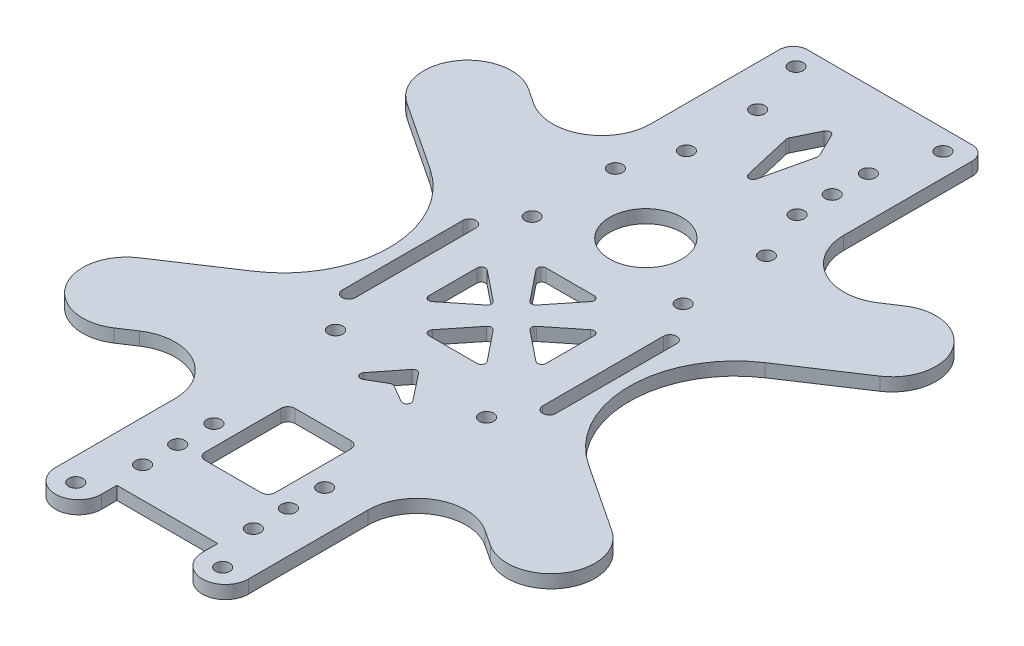
SolidWorks part; units mm, degrees
ref_plane "Front Plane" through (0, 0, 0) normal (0, 0, 1) x (1, 0, 0)
ref_plane "Top Plane" through (0, 0, 0) normal (0, 1, 0) x (1, 0, 0)
ref_plane "Right Plane" through (0, 0, 0) normal (1, 0, 0) x (0, 0, -1)
sketch "Sketch1" plane through (0, 0, 0) normal (0, 1, 0) x (1, 0, 0)
  line L0 (0, 68.8578) -> (0, -61.9125)
  line L1 (17.4625, -68.8578) -> (9.1281, -68.8578)
  line L2 (17.4625, -68.8578) -> (17.4625, -26.5137)
  line L3 (17.4625, 68.8578) -> (-17.4625, 68.8578)
  line L4 (-17.4625, -68.8578) -> (-17.4625, -26.5137)
  line L5 (17.4625, -68.8578) -> (-17.4625, 68.8578) construction
  line L6 (17.4625, 68.8578) -> (-17.4625, -68.8578) construction
  line L7 (9.1281, -68.8578) -> (9.1281, -61.9125)
  line L8 (9.1281, -61.9125) -> (-9.1281, -61.9125)
  line L9 (-9.1281, -68.8578) -> (-17.4625, -68.8578)
  line L10 (0, -16.2719) -> (6.8741, -25.0031)
  line L11 (-6.35, -50.0063) -> (6.35, -50.0063)
  line L12 (-6.35, -50.0063) -> (-6.35, -33.7344)
  line L13 (-6.35, -33.7344) -> (6.35, -33.7344)
  line L14 (6.35, -50.0063) -> (6.35, -33.7344)
  line L15 (-6.35, -50.0063) -> (6.35, -33.7344) construction
  line L16 (-6.35, -33.7344) -> (6.35, -50.0063) construction
  line L17 (6.8741, -25.0031) -> (0, -21.0344)
  line L18 (0, -2.7781) -> (5.9531, -10.2136)
  line L19 (5.9531, -10.2136) -> (-5.9531, -10.2136)
  line L20 (-5.9531, -10.2136) -> (0, -2.7781)
  line L21 (-10.6105, 6.35) -> (-3.175, 0.3969)
  line L22 (-3.175, 0.3969) -> (-10.6105, -5.5562)
  line L23 (-10.6105, -5.5562) -> (-10.6105, 6.35)
  line L24 (5.9531, 11.0073) -> (0, 3.5719)
  line L25 (0, 3.5719) -> (-5.9531, 11.0073)
  line L26 (-5.9531, 11.0073) -> (5.9531, 11.0073)
  line L27 (10.6105, -5.5563) -> (3.175, 0.3969)
  line L28 (3.175, 0.3969) -> (10.6105, 6.35)
  line L29 (10.6105, 6.35) -> (10.6105, -5.5563)
  line L30 (18.1511, 10.9234) -> (18.1511, -10.9234) construction
  line L31 (19.3417, 10.9234) -> (19.3417, -10.9234)
  line L32 (16.9605, 10.9234) -> (16.9605, -10.9234)
  line L33 (-55, 0) -> (55, 0) construction
  line L34 (0, 59.0292) -> (2.8661, 53.1453)
  line L35 (2.8661, 53.1453) -> (0, 40.773)
  line L36 (17.4625, 26.5137) -> (40.6519, 41.8703)
  line L37 (40.6519, 41.8703) -> (49.4171, 28.6344)
  line L38 (49.4171, 28.6344) -> (21.723, 10.2947)
  line L39 (49.4171, -28.6344) -> (21.723, -10.2947)
  line L40 (40.6519, -41.8703) -> (49.4171, -28.6344)
  line L41 (17.4625, -26.5137) -> (40.6519, -41.8703)
  line L42 (21.723, 10.2947) -> (21.723, -10.2947)
  line L43 (-17.4625, -26.5137) -> (-40.6519, -41.8703)
  line L44 (-40.6519, -41.8703) -> (-49.4171, -28.6344)
  line L45 (-49.4171, -28.6344) -> (-21.723, -10.2947)
  line L46 (-21.723, 10.2947) -> (-21.723, -10.2947)
  line L47 (-49.4171, 28.6344) -> (-21.723, 10.2947)
  line L48 (-40.6519, 41.8703) -> (-49.4171, 28.6344)
  line L49 (-17.4625, 26.5137) -> (-40.6519, 41.8703)
  line L50 (-9.1281, -68.8578) -> (-9.1281, -61.9125)
  line L51 (-18.1511, 10.9234) -> (-18.1511, -10.9234) construction
  line L52 (-19.3417, 10.9234) -> (-19.3417, -10.9234)
  line L53 (-16.9605, 10.9234) -> (-16.9605, -10.9234)
  line L54 (-2.8661, 53.1453) -> (0, 40.773)
  line L55 (0, 59.0292) -> (-2.8661, 53.1453)
  line L56 (17.4625, 26.5137) -> (17.4625, 68.8578)
  line L57 (-17.4625, 26.5137) -> (-17.4625, 68.8578)
  line L58 (-6.8741, -25.0031) -> (0, -21.0344)
  line L59 (0, -16.2719) -> (-6.8741, -25.0031)
  circle A0 centre (13.2953, -65.1867) radius 1.2898
  circle A1 centre (10.0211, -50.0063) radius 1.2898
  circle A2 centre (10.0211, -43.4578) radius 1.2898
  circle A3 centre (10.0211, -56.3563) radius 1.2898
  circle A4 centre (0, 24.6995) radius 6.5484
  circle A5 centre (10.0211, 54.9672) radius 1.2898
  circle A6 centre (10.0211, 48.4187) radius 1.2898
  circle A7 centre (10.0211, 42.0687) radius 1.2898
  arc A8 (19.3417, 10.9234) -> (16.9605, 10.9234) centre (18.1511, 10.9234) ccw
  arc A9 (16.9605, -10.9234) -> (19.3417, -10.9234) centre (18.1511, -10.9234) ccw
  circle A10 centre (13.671, -17.7895) radius 1.2898
  circle A11 centre (13.671, 17.7895) radius 1.2898
  circle A12 centre (13.671, 32.8707) radius 1.2898
  circle A13 centre (13.2953, 65.1867) radius 1.2898
  circle A14 centre (-13.2953, -65.1867) radius 1.2898
  circle A15 centre (-10.0211, -56.3562) radius 1.2898
  circle A16 centre (-10.0211, -50.0062) radius 1.2898
  circle A17 centre (-10.0211, -43.4578) radius 1.2898
  circle A18 centre (-13.671, -17.7895) radius 1.2898
  arc A19 (-19.3417, 10.9234) -> (-16.9605, 10.9234) centre (-18.1511, 10.9234) cw
  arc A20 (-16.9605, -10.9234) -> (-19.3417, -10.9234) centre (-18.1511, -10.9234) cw
  circle A21 centre (-13.671, 17.7895) radius 1.2898
  circle A22 centre (-13.671, 32.8707) radius 1.2898
  circle A23 centre (-10.0211, 42.0688) radius 1.2898
  circle A24 centre (-10.0211, 54.9672) radius 1.2898
  circle A25 centre (-13.2953, 65.1867) radius 1.2898
  point P0 (0, 0)
  point P10 (9.1281, -65.3852)
  point P17 (13.2953, -68.8578)
  point P18 (0, -41.8703)
  point P26 (18.1511, 0)
  point P46 (0, 0.3969)
  point P88 (0, -61.9125)
  point P100 (-18.1511, 0)
  point P111 (-10.0211, 48.4188)
  dimension "D4" = 2.5797
  dimension "D5" = 2.3813
  dimension "D11" = 10.3187
  dimension "D12" = 2.5797
  dimension "D13" = 2.5797
  dimension "D14" = 13.0969
  dimension "D23" = 7.1437
  dimension "D25" = 3.9688
  dimension "D27" = 1.1906
  dimension "D28" = 24.228
  dimension "D30" = 9.525
  dimension "D1" = 137.7156
  dimension "D2" = 34.925
  dimension "D3" = 8.3344
  dimension "D6" = 6.9453
  dimension "D7" = 16.2719
  dimension "D8" = 12.7
  dimension "D9" = 11.9062
  dimension "D10" = 2.3813
  dimension "D15" = 12.7
  dimension "D16" = 7.9375
  dimension "D17" = 11.1125
  dimension "D18" = 4.7625
  dimension "D19" = 9.525
  dimension "D20" = 11.9062
  dimension "D21" = 2.7781
  dimension "D26" = 6.35
  dimension "D29" = 6.35
  dimension "D31" = 2
  dimension "D32" = 9.525
  dimension "D33" = 18.2562
  dimension "D34" = 12.7
  dimension "D35" = 6.5448
  dimension "D36" = 15.875
  dimension "D37" = 26.9875
  dimension "D38" = 2.3813
  dimension "D24" = 2
  dimension "D22" = 4
extrude "Boss-Extrude1" add sketch "Sketch1" along normal mid plane 2.3813 contours A4 L0 L54 L55 L3 L57 L49 L48 L47 L46 L45 L44 L43 L4 L9 L50 L8 L11 L12 L13 L19 L20 L25 L26 A25 A23 A22 A21 A17 A15 L22 L23 L21 A14 A16 | A4 L0 L26 L24 L18 L19 L10 L17 L13 L14 L11 L8 L7 L1 L2 L41 L40 L39 L42 L38 L37 L36 L56 L3 L34 L35 A12 L28 L29 L27 A0 A1 A2 A3 A5 A6 region at (8.7312, 0, -67.3947) region at (-1.4631, 0, -63.9435)
fillet "Fillet1" 2 edges at (-17.4625, 0, 68.8578) (-9.1281, 0, 68.8578) type full round first side face at (-17.4625, 0, 47.6858) second side face at (-9.1281, 0, 65.3852) middle face at (-13.2953, 0, 68.8578)
fillet "Fillet2" 2 edges at (9.1281, 0, 68.8578) (17.4625, 0, 68.8578) type full round first side face at (9.1281, 0, 65.3852) second side face at (17.4625, 0, 47.6858) middle face at (13.2953, 0, 68.8578)
fillet "Fillet3" 2 edges at (40.6519, 0, -41.8703) (49.4171, 0, -28.6344) type full round first side face at (29.0572, 0, -34.192) second side face at (35.57, 0, -19.4646) middle face at (45.0345, 0, -35.2524)
fillet "Fillet4" 2 edges at (40.6519, 0, 41.8703) (49.4171, 0, 28.6344) type full round first side face at (29.0572, 0, 34.192) second side face at (35.57, 0, 19.4646) middle face at (45.0345, 0, 35.2524)
fillet "Fillet5" 2 edges at (-49.4171, 0, 28.6344) (-40.6519, 0, 41.8703) type full round first side face at (-35.57, 0, 19.4646) second side face at (-29.0572, 0, 34.192) middle face at (-45.0345, 0, 35.2524)
fillet "Fillet6" 2 edges at (-40.6519, 0, -41.8703) (-49.4171, 0, -28.6344) type full round first side face at (-29.0572, 0, -34.192) second side face at (-35.57, 0, -19.4646) middle face at (-45.0345, 0, -35.2524)
fillet "Fillet7" 2 edges at (-21.723, 0, -10.2947) (-21.723, 0, 10.2947) type full round first side face at (-32.261, 0, -17.2733) second side face at (-32.261, 0, 17.2733) middle face at (-21.723, 0, 0)
fillet "Fillet8" 2 edges at (21.723, 0, -10.2947) (21.723, 0, 10.2947) type full round first side face at (32.261, 0, -17.2733) second side face at (32.261, 0, 17.2733) middle face at (21.723, 0, 0)
fillet "Fillet9" radius 8.89 4 edges at (-17.4625, 0, -26.5137) (17.4625, 0, 26.5137) (-17.4625, 0, 26.5137) (17.4625, 0, -26.5137)
fillet "Fillet10" radius 2.54 2 edges at (17.4625, 0, -68.8578) (-17.4625, 0, -68.8578)
fillet "Fillet11" radius 0.762 20 edges at (0, 0, -40.773) (2.8661, 0, -53.1453) (-2.8661, 0, -53.1453) (0, 0, -59.0292) (6.8741, 0, 25.0031) (0, 0, 21.0344) (-6.8741, 0, 25.0031) (0, 0, 16.2719) (-3.175, 0, -0.3969) (-10.6105, 0, -6.35) (-10.6105, 0, 5.5562) (-5.9531, 0, 10.2136) (0, 0, 2.7781) (5.9531, 0, 10.2136) (10.6105, 0, 5.5563) (3.175, 0, -0.3969) (10.6105, 0, -6.35) (0, 0, -3.5719) (5.9531, 0, -11.0073) (-5.9531, 0, -11.0073)
fillet "Fillet14" radius 1.27 4 edges at (6.35, 0, 33.7344) (6.35, 0, 50.0063) (-6.35, 0, 33.7344) (-6.35, 0, 50.0063)
